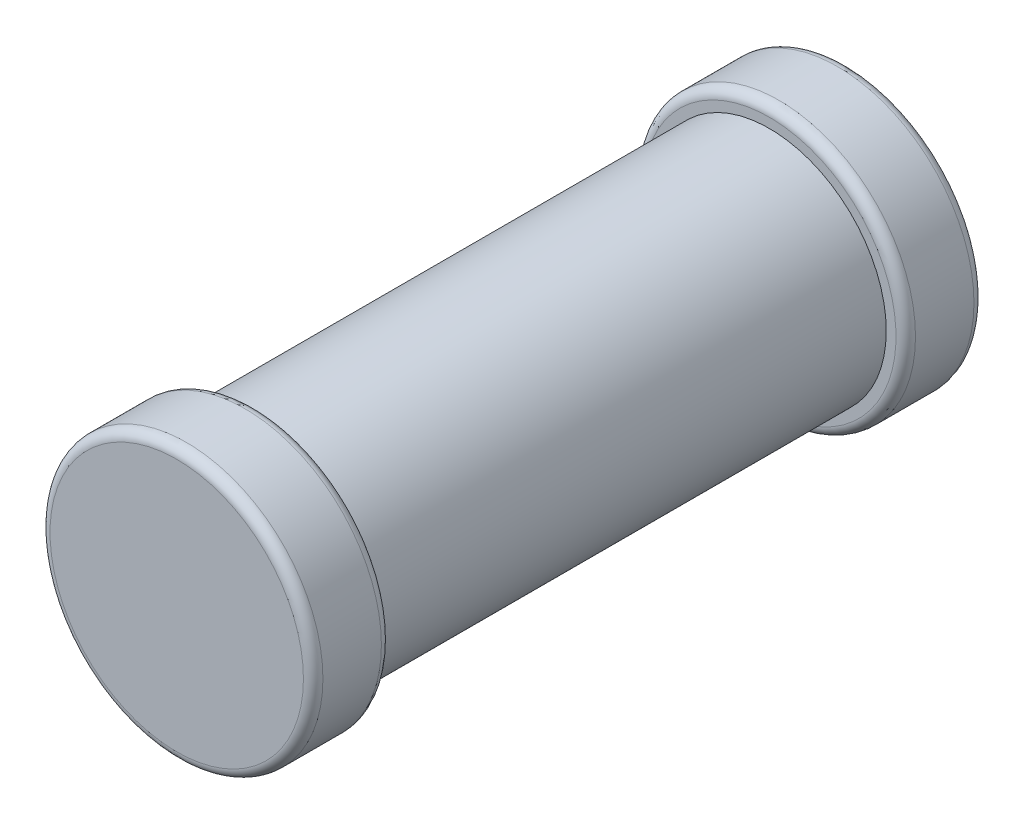
SolidWorks part; units mm, degrees
ref_plane "Plano frontal" through (0, 0, 0) normal (0, 0, 1) x (1, 0, 0)
ref_plane "Plano superior" through (0, 0, 0) normal (0, 1, 0) x (1, 0, 0)
ref_plane "Plano direito" through (0, 0, 0) normal (1, 0, 0) x (0, 0, -1)
sketch "Esboço1" plane through (0, 0, 0) normal (0, 0, 1) x (1, 0, 0)
  circle A0 centre (0, 0) radius 0.6
  dimension "D1" = 1.2
extrude "Extrusão1" add sketch "Esboço1" along normal blind 1.32 and the other way blind 1.32
sketch "Esboço2" plane through (0, 0, 1.32) normal (0, 0, 1) x (1, 0, 0)
  circle A0 centre (0, 0) radius 0.7
  dimension "D1" = 1.4
extrude "Extrusão2" add sketch "Esboço2" along normal blind 0.4
fillet "Filete1" radius 0.05 2 edges at (0.7, 0, 1.72) (0.7, 0, 1.32)
mirror "Espelhar1" about plane through (0, 0, 0) normal (0, 0, 1) of "Filete1", "Extrusão2"
